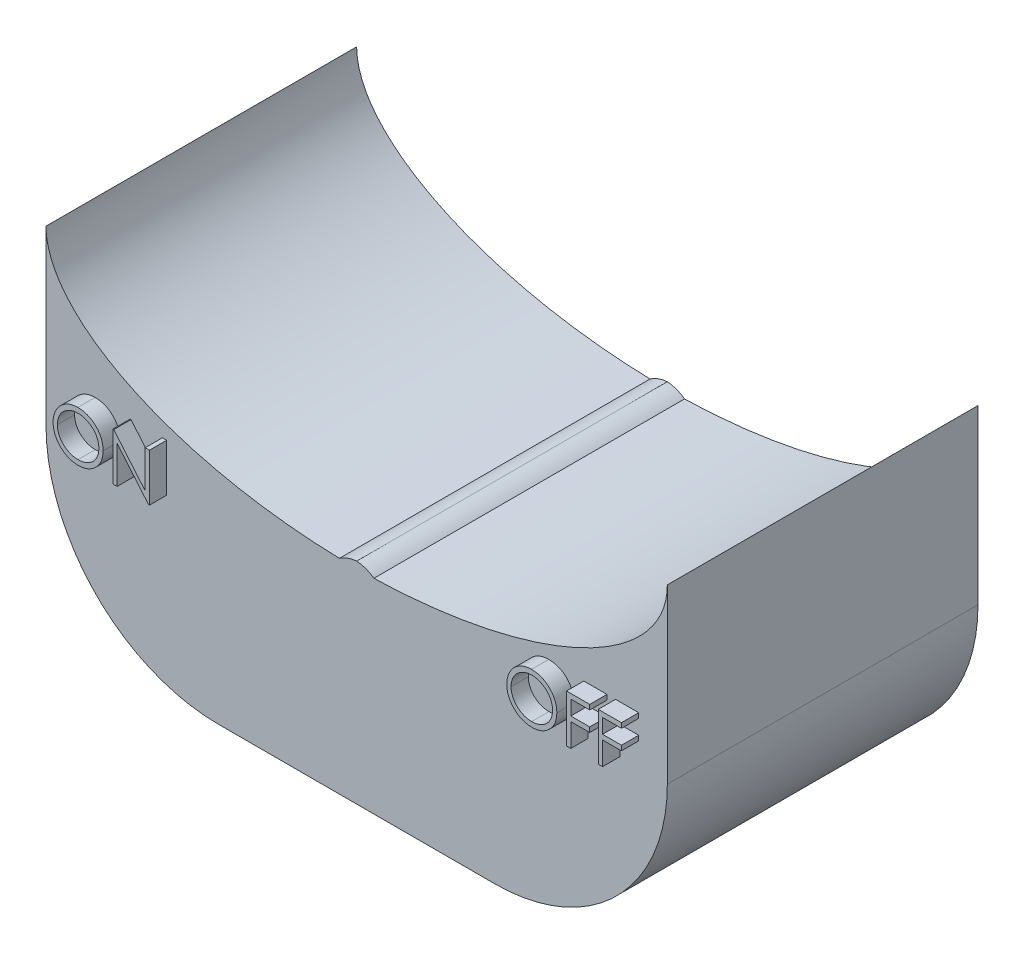
SolidWorks part; units mm, degrees
material "POM Acetal Copolymer"
ref_plane "Front Plane" through (0, 0, 0) normal (0, 0, 1) x (1, 0, 0)
ref_plane "Top Plane" through (0, 0, 0) normal (0, 1, 0) x (1, 0, 0)
ref_plane "Right Plane" through (0, 0, 0) normal (1, 0, 0) x (0, 0, -1)
sketch "Sketch1" plane through (0, 0, 0) normal (0, 0, 1) x (1, 0, 0)
  line L0 (-22.86, 0) -> (-22.86, -25.4)
  line L1 (-22.86, -25.4) -> (22.86, -25.4)
  line L2 (22.86, -25.4) -> (22.86, 0)
  ellipse E0 centre (0, 0) end of major axis (22.86, 0) minor radius 10.3902 (-22.86, 0) -> (22.86, 0) ccw
  dimension "D1" = 10.3902
  dimension "D2" = 45.72
  dimension "D3" = 25.4
extrude "Boss-Extrude1" add sketch "Sketch1" along normal blind 22.86
sketch "Sketch2" plane through (0, 0, 22.86) normal (0, 0, 1) x (1, 0, 0)
  line L0 (-22.86, 0) -> (-22.86, -25.4) construction
  line L1 (-22.86, -25.4) -> (22.86, -25.4) construction
  text T0 "ON                   OFF"
  dimension "D1" = 1.524
  dimension "D2" = 12.7
extrude "Boss-Extrude2" add sketch "Sketch2" along normal blind 1.27
fillet "Fillet1" radius 12.7 2 edges at (22.86, -25.4, 11.43) (-22.86, -25.4, 11.43)
sketch "Sketch3" plane through (0, 0, 0) normal (0, 0, -1) x (-1, 0, 0)
  line L0 (-1.27, -11.176) -> (-1.27, -9.906)
  line L1 (-1.27, -9.906) -> (1.27, -9.906)
  line L2 (1.27, -9.906) -> (1.27, -11.176)
  line L3 (1.27, -11.176) -> (-1.27, -11.176)
  point P4 (0, -9.906)
  dimension "D1" = 9.906
  dimension "D2" = 2.54
  dimension "D3" = 1.27
extrude "Boss-Extrude3" add sketch "Sketch3" against normal blind 22.86
fillet "Fillet2" radius 2.54 2 edges at (-1.27, -9.906, 11.43) (1.27, -9.906, 11.43)
